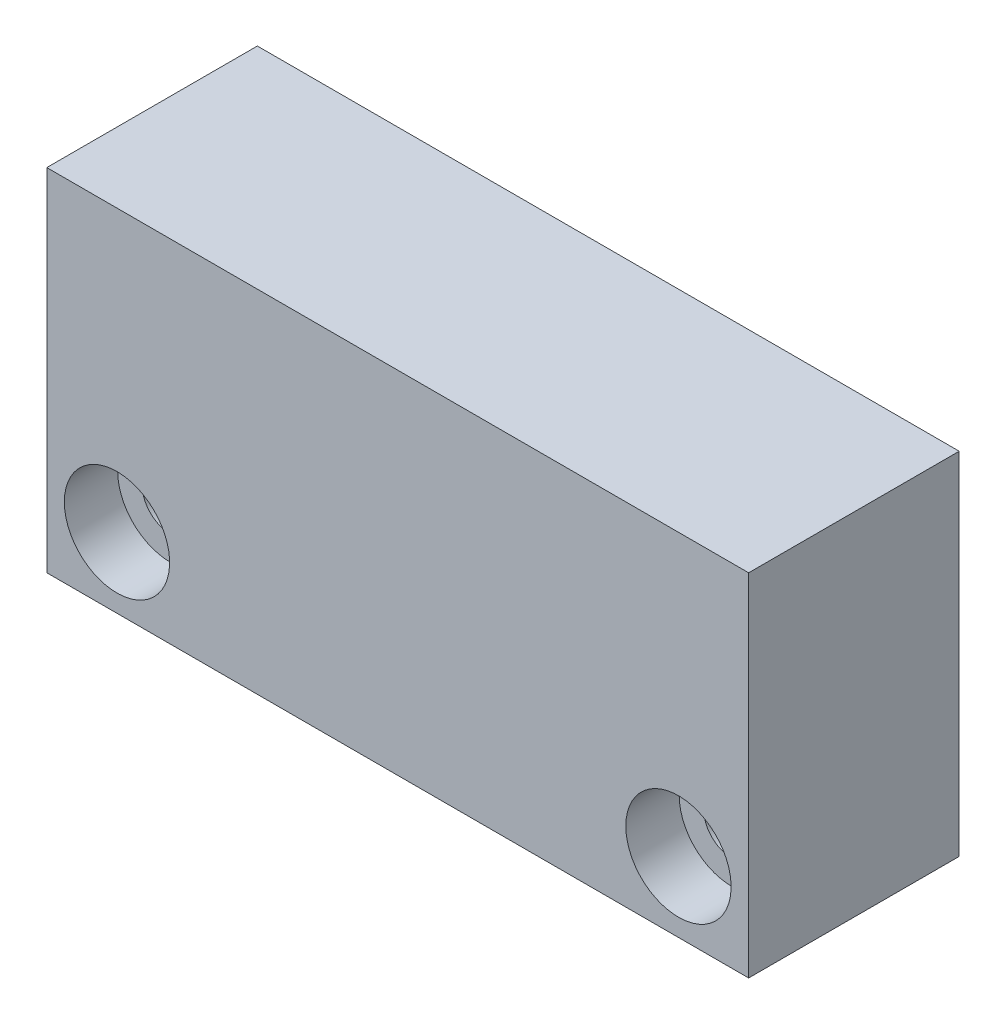
SolidWorks part; units mm, degrees
ref_plane "Front" through (0, 0, 0) normal (0, 0, 1) x (1, 0, 0)
ref_plane "Top" through (0, 0, 0) normal (0, 1, 0) x (1, 0, 0)
ref_plane "Right" through (0, 0, 0) normal (1, 0, 0) x (0, 0, -1)
sketch "Sketch1" plane through (0, 0, 0) normal (0, 0, 1) x (1, 0, 0)
  line L1 (-27.6031, 11.7281) -> (35.8969, 11.7281)
  line L2 (-27.6031, 11.7281) -> (-27.6031, -20.0219)
  line L3 (-27.6031, -20.0219) -> (35.8969, -20.0219)
  line L4 (35.8969, 11.7281) -> (35.8969, -20.0219)
  circle A0 centre (-21.2531, -13.6719) radius 4.7625
  circle A1 centre (29.5469, -13.6719) radius 4.7625
  circle A2 centre (-21.2531, -13.6719) radius 2.5527
  circle A3 centre (29.5469, -13.6719) radius 2.5527
  dimension "D3" = 6.35
  dimension "D4" = 6.35
  dimension "D1" = 31.75
  dimension "D2" = 63.5
  dimension "D5" = 6.35
  dimension "D6" = 6.35
extrude "Boss-Extrude1" add sketch "Sketch1" along normal blind 19.05 contours L4 L1 L2 L3 A1 A0 region at (4.1469, -3.4224, 0)
extrude "Boss-Extrude2" add sketch "Sketch1<3>" along normal blind 14.224 contours A0 A2 | A1 A3 region at (-25.8809, -13.6719, 0) region at (24.9191, -13.6719, 0)
sketch "Sketch1<3>" plane through (0, 0, 0) normal (0, 0, 1) x (1, 0, 0) same geometry as "Sketch1"
